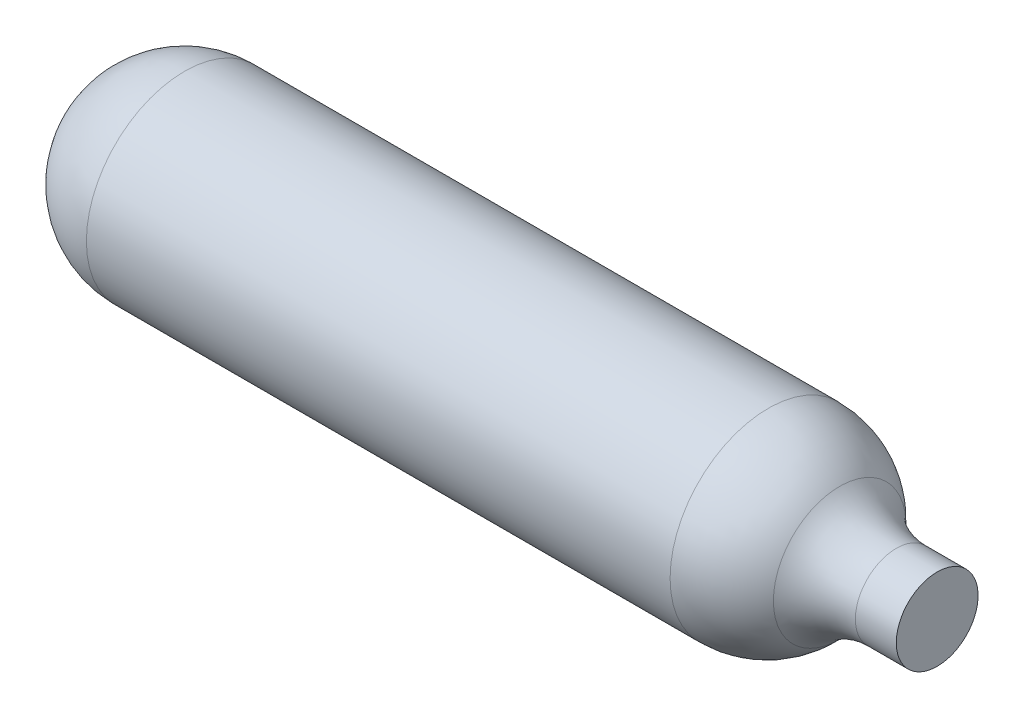
SolidWorks part; units mm, degrees
ref_plane "Front Plane" through (0, 0, 0) normal (0, 0, 1) x (1, 0, 0)
ref_plane "Top Plane" through (0, 0, 0) normal (0, 1, 0) x (1, 0, 0)
ref_plane "Right Plane" through (0, 0, 0) normal (1, 0, 0) x (0, 0, -1)
sketch "Sketch1" plane through (0, 0, 0) normal (0, 0, 1) x (1, 0, 0)
  line L0 (0, 0) -> (82.55, 0)
  line L1 (82.55, 0) -> (82.55, 3.9688)
  line L2 (82.55, 3.9688) -> (78.5812, 3.9687)
  line L3 (9.525, 9.525) -> (66.1617, 9.525)
  circle A0 centre (9.525, 0) radius 9.525
  arc A1 (66.1617, 9.525) -> (73.0857, 6.4273) centre (66.1617, 0.2377) cw
  arc A2 (73.0857, 6.4273) -> (78.5812, 3.9687) centre (78.5812, 11.3399) ccw
  point P12 (67.7259, 9.525)
  point P13 (75.571, 4.9272)
  point P14 (66.3798, 1.6061)
  point P15 (70.9754, 6.234)
  point P16 (73.0857, 6.4273)
  dimension "D2" = 19.05
  dimension "D3" = 3.9688
  dimension "D1" = 82.55
  dimension "D4" = 3.9688
revolve "Revolve1" add sketch "Sketch1" angle 360 about L0 region at (9.525, 4.0425, 0) region at (47.0791, 4.6239, 0)
